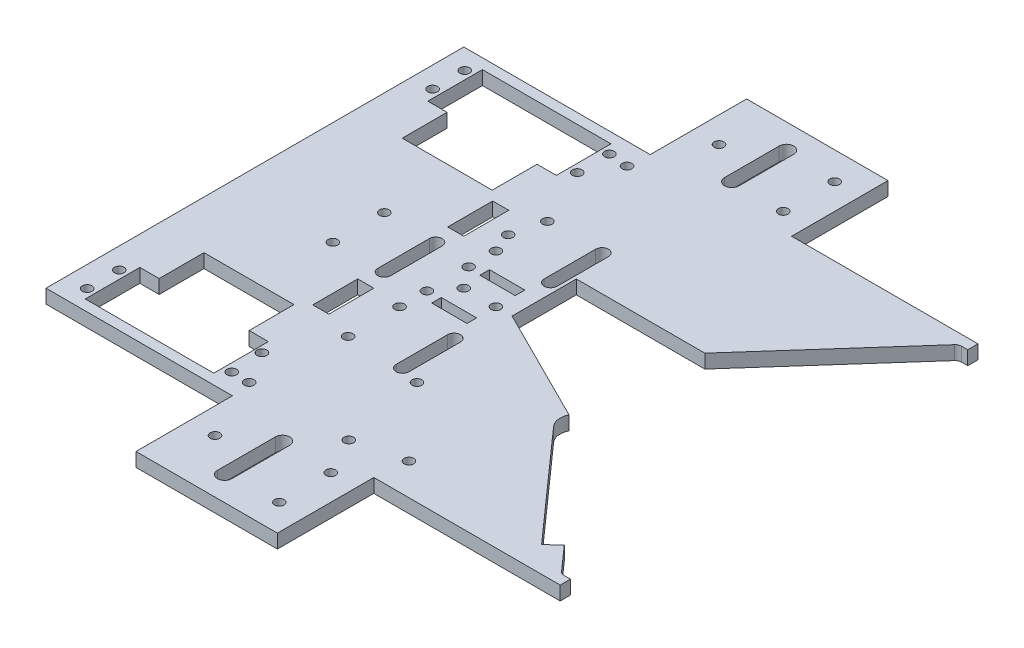
SolidWorks part; units mm, degrees
material "Acrylic (Medium-high impact)"
ref_plane "Front Plane" through (0, 0, 0) normal (0, 0, 1) x (1, 0, 0)
ref_plane "Top Plane" through (0, 0, 0) normal (0, 1, 0) x (1, 0, 0)
ref_plane "Right Plane" through (0, 0, 0) normal (1, 0, 0) x (0, 0, -1)
sketch "Sketch2" plane through (0, 0, 0) normal (0, 1, 0) x (1, 0, 0)
  line L2 (0, 0) -> (0, 65)
  line L3 (0, 65) -> (58, 65)
  line L4 (160, 0) -> (160, 65)
  line L8 (0, 0) -> (160, 0)
  line L9 (102, 65) -> (160, 65)
  line L11 (102, 65) -> (102, 95)
  line L12 (58, 65) -> (58, 95)
  line L13 (58, 95) -> (102, 95)
  dimension "D1" = 65
  dimension "D2" = 160
  dimension "D3" = 44
  dimension "D4" = 30
extrude "Boss-Extrude1" add sketch "Sketch2" along normal blind 4.3
mirror "Mirror1" about plane through (0, 4.3, 0) normal (0, 0, -1) of bodies 101
sketch "Sketch3" plane through (0, 4.3, 0) normal (0, 1, 0) x (1, 0, 0)
  line L0 (160, 61.8) -> (160, -61.8)
  line L1 (120.0126, 20) -> (157.1565, 61.8)
  line L3 (80.0126, 0) -> (80.0126, 20)
  line L4 (80.0126, 20) -> (120.0126, 20)
  line L12 (160, 65) -> (102, 65)
  line L13 (102, 65) -> (102, 95)
  line L15 (102, 95) -> (58, 95)
  line L16 (58, 65) -> (0, 65)
  line L17 (0, 65) -> (0, -65)
  line L18 (0, -65) -> (58, -65)
  line L20 (58, 95) -> (58, 65)
  line L22 (102, -65) -> (160, -65)
  line L23 (160, -65) -> (160, 65)
  line L36 (58, -65) -> (58, -95)
  line L38 (58, -95) -> (102, -95)
  line L39 (58, -95) -> (102, -95)
  line L40 (102, -95) -> (102, -65)
  line L42 (160, -61.8) -> (157.1556, -61.8)
  line L45 (160, 61.8) -> (157.1565, 61.8)
  line L48 (80.0126, 0) -> (120, -20)
  line L49 (120, -20) -> (157.1556, -61.8)
  line M24 (160, -65) -> (160, 65)
  dimension "D2" = 130
  dimension "D3" = 20
  dimension "D4" = 40
  dimension "D1" = 0
extrude "Cut-Extrude1" cut sketch "Sketch3" against normal blind 4.5 contours L48 L49 L1 L4 L3 M24 region at (132.7054, 4.3, -1.1594)
fillet "Fillet1" radius 2 2 edges at (157.1565, 2.15, -61.8) (157.1556, 2.15, 61.8)
ref_axis "Axis1" through (80, 4.3, 95) along (0, 0, -1)
sketch "Sketch4" plane through (0, 4.3, 0) normal (0, 1, 0) x (1, 0, 0)
  line L0 (80, -95) -> (80, 95)
  line L1 (102, -95) -> (58, -95) construction
  line L2 (102, 95) -> (58, 95) construction
ref_plane "Plane2" through (0, 4.3, 0) normal (0, 1, 0) x (1, 0, 0)
sketch "Sketch6" plane through (0, 4.3, 0) normal (0, 1, 0) x (1, 0, 0)
  line L3 (9, -61.8) -> (49, -61.8)
  line L6 (29, -45.8) -> (29, -44.8)
  line L7 (9, -44.8) -> (15, -44.8)
  line L11 (43, -44.8) -> (43, -30.8418)
  line L12 (15, -44.8) -> (15, -30.8418)
  line L13 (15, -30.8418) -> (43, -30.8418)
  line L15 (0, 0) -> (80.0126, 0)
  line L16 (80.0126, 0) -> (120, -20) construction
  line L18 (9, 44.8) -> (15, 44.8)
  line L20 (15, 30.8418) -> (43, 30.8418)
  line L21 (15, 44.8) -> (15, 30.8418)
  line L22 (43, 44.8) -> (43, 30.8418)
  line L25 (15, -45.8) -> (15, -30.8418) construction
  line L27 (9, 61.8) -> (49, 61.8)
  line L30 (4, -61.8) -> (3, -61.8)
  line L31 (0, -61.8) -> (160, -61.8) construction
  line L32 (3, -61.8) -> (4, -61.8)
  line L33 (3, -44.8) -> (3, -62.8) construction
  line L34 (3, -62.8) -> (55, -62.8) construction
  line L35 (55, -44.8) -> (55, -62.8) construction
  line L36 (4, -61.8) -> (54, -61.8) construction
  line L37 (0, 61.8) -> (160, 61.8) construction
  line L38 (54, 61.8) -> (55, 61.8)
  line L39 (54, 61.8) -> (55, 61.8)
  line L40 (43, 44.8) -> (49, 44.8)
  line L41 (4, -45.8) -> (4, -61.8) construction
  line L42 (4, -45.8) -> (54, -45.8) construction
  line L43 (43, -44.8) -> (49, -44.8)
  line L44 (3, -44.8) -> (55, -44.8) construction
  line L45 (29, -45.8) -> (29, -30.8418) construction
  line L46 (43, -45.8) -> (43, -30.8418) construction
  line L47 (54, -45.8) -> (54, -61.8) construction
  line L48 (9, -61.8) -> (49, -61.8)
  line L52 (9, 61.8) -> (9, 44.8)
  line L53 (55, 61.8) -> (54, 61.8)
  line L56 (49, 61.8) -> (49, 44.8)
  line L59 (3, -61.8) -> (4, -61.8)
  line L60 (9, -44.8) -> (9, -61.8)
  line L64 (49, -44.8) -> (49, -61.8)
  dimension "D4" = 1
  dimension "D5" = 14
  dimension "D6" = 14
extrude "Cut-Extrude2" cut sketch "Sketch6" against normal blind 10
sketch "Sketch8" plane through (0, 4.3, 0) normal (0, 1, 0) x (1, 0, 0)
  circle A0 centre (6.5, 58.8) radius 1.5
  circle A1 centre (6.5, 48.8) radius 1.5
  circle A2 centre (51.5, 48.8) radius 1.5
  circle A3 centre (51.5, 58.8) radius 1.5
  circle A4 centre (6.5, -48.7) radius 1.5
  circle A5 centre (6.5, -58.7) radius 1.5
  circle A6 centre (51.5, -58.7) radius 1.5
  circle A7 centre (51, -48.8) radius 1.5
  dimension "D7" = 3
extrude "Cut-Extrude3" cut sketch "Sketch8" against normal blind 10
sketch "Sketch9" plane through (0, 0, 0) normal (0, -1, 0) x (1, 0, 0)
  line L0 (75.75, 69.4) -> (75.75, 87.4)
  line L1 (75.75, -87.4) -> (75.75, -70.4)
  line L2 (80.25, -87.4) -> (80.25, -70.4)
  line L4 (80.25, 69.4) -> (80.25, 87.4)
  circle A0 centre (94, 70.4) radius 1.5
  circle A1 centre (66, 78.4) radius 1.5
  circle A2 centre (66, -78.4) radius 1.5
  circle A3 centre (94, -86.4) radius 1.5
  circle A4 centre (94, 86.4) radius 1.5
  circle A5 centre (94, -70.4) radius 1.5
  arc A6 (75.75, -87.4) -> (80.25, -87.4) centre (78, -87.4) ccw
  arc A7 (80.25, -70.4) -> (75.75, -70.4) centre (78, -70.4) ccw
  arc A10 (75.75, 69.4) -> (80.25, 69.4) centre (78, 69.4) ccw
  arc A12 (80.25, 87.4) -> (75.75, 87.4) centre (78, 87.4) ccw
  dimension "D1" = 3
extrude "Cut-Extrude4" cut sketch "Sketch9" against normal blind 10
sketch "Sketch7" plane through (0, 4.3, 0) normal (0, 1, 0) x (1, 0, 0)
  line L0 (0, 0) -> (80.0126, 0)
  line L1 (0, 65) -> (0, -65) construction
  line L2 (80.0126, 0) -> (80.0126, 20) construction
  line L3 (80, -95) -> (80, 95) construction
  line L4 (64, -9) -> (75, -9)
  line L5 (64, -6) -> (75, -6)
  line L6 (64, -9) -> (64, -6)
  line L7 (75, -9) -> (75, -6)
  line L8 (64, -7.5) -> (75, -7.5)
  line L9 (64, 7.5) -> (75, 7.5)
  line L10 (75, 9) -> (75, 6)
  line L11 (64, 9) -> (64, 6)
  line L12 (64, 6) -> (75, 6)
  line L13 (64, 9) -> (75, 9)
  circle A0 centre (60.0126, -6.5) radius 1.5
  circle A1 centre (60.0126, 6.5) radius 1.5
  dimension "D1" = 3
  dimension "D2" = 6.5
  dimension "D3" = 20
  dimension "D6" = 11
  dimension "D4" = 5
  dimension "D5" = 3
  dimension "D7" = 7.5
sketch "Sketch10" plane through (0, 4.3, 0) normal (0, 1, 0) x (1, 0, 0)
  line L0 (120, -20) -> (156.5589, -61.1287) construction
  line L1 (123.3218, -23.737) -> (149.8964, -53.6334)
  line L2 (116.263, -23.3218) -> (146.1593, -56.9552)
  line L3 (149.8964, -53.6334) -> (146.1593, -56.9552)
  line L4 (120, -20) -> (156.5589, -61.1287) construction
  line L5 (116.263, -23.3218) -> (152.8218, -64.4505) construction
  arc A0 (123.3218, -23.737) -> (116.263, -23.3218) centre (120, -20) ccw
  dimension "D1" = 5
  dimension "D2" = 45
extrude "Cut-Extrude5" cut sketch "Sketch10" against normal blind 10
sketch "Sketch11" plane through (0, 0, 0) normal (0, -1, 0) x (1, 0, 0)
  line L0 (0, 0) -> (80.0126, 0) construction
  line L1 (80, 95) -> (80, -95) construction
  line L2 (80.0126, 0) -> (0, 0)
  line L4 (75, 31.0313) -> (75, 15.0313)
  line L6 (79, 31.0313) -> (79, 15.0313)
  line L7 (79, -31.0313) -> (79, -15.0313)
  line L8 (75, -31.0313) -> (75, -15.0313)
  circle A0 centre (60, 31) radius 1.5
  circle A1 centre (60, 15) radius 1.5
  arc A2 (75, 31.0313) -> (79, 31.0313) centre (77, 31.0313) cw
  arc A3 (75, 15.0313) -> (79, 15.0313) centre (77, 15.0313) ccw
  arc A4 (75, -15.0313) -> (79, -15.0313) centre (77, -15.0313) cw
  arc A5 (75, -31.0313) -> (79, -31.0313) centre (77, -31.0313) ccw
  circle A6 centre (60, -15) radius 1.5
  circle A7 centre (60, -31) radius 1.5
  dimension "D1" = 3
  dimension "D2" = 16
  dimension "D3" = 15
  dimension "D4" = 20
  dimension "D5" = 15
  dimension "D6" = 4
extrude "Cut-Extrude6" cut sketch "Sketch11" against normal blind 10 contours L4 A3 L6 A2 | L8 A5 L7 A4 | A7 | A0 | A1 | A6 region at (77, 0, 23.0313) region at (77, 0, -23.0313) region at (60, 0, -31)
sketch "Sketch12" plane through (0, 0, 0) normal (0, -1, 0) x (-1, 0, 0)
  line L0 (0, 0) -> (-80.0126, 0) construction
  line L3 (-50.2627, -8) -> (-50.2627, 8)
  line L4 (-50.2627, 0) -> (-46.2627, 0)
  line L5 (-46.2627, -8) -> (-46.2627, 8)
  line L6 (0, 0) -> (-46.2627, 0)
  line L7 (0, 65) -> (0, -65) construction
  line L8 (-160, -61.8) -> (0, -61.8) construction
  line L9 (-80.0126, 0) -> (-50.2627, 0)
  line L10 (-80.0126, 0) -> (-115.5281, -17.7634) construction
  line L11 (-80.0126, 0) -> (-80.0126, 20) construction
  line L12 (-58, -65) -> (0, -65) construction
  line L13 (-58, 65) -> (0, 65) construction
  circle A0 centre (-32.2627, -8) radius 1.5
  circle A1 centre (-32.2627, 8) radius 1.5
  arc A2 (-46.2627, 8) -> (-50.2627, 8) centre (-48.2627, 8) ccw
  arc A3 (-50.2627, -8) -> (-46.2627, -8) centre (-48.2627, -8) ccw
  circle A5 centre (-32.2627, -8) radius 1.5 construction
  circle A6 centre (-32.2627, 8) radius 1.5 construction
  dimension "D1" = 3
  dimension "D8" = 8
  dimension "D9" = 8
  dimension "D2" = 8
  dimension "D3" = 14
  dimension "D4" = 4
  dimension "D5" = 61.8
  dimension "D6" = 65
  dimension "D7" = 65
extrude "Cut-Extrude7" cut sketch "Sketch12" against normal blind 10 contours A3 L5 L4 L3 | L4 L5 A2 L3 | A0 | A1 region at (48.2627, 0, 4.7958) region at (48.2627, 0, -4.7958) region at (32.2627, 0, 8) region at (32.2627, 0, -8)
extrude "Cut-Extrude8" cut sketch "Sketch7" against normal blind 9 contours A0 | L4 L7 L5 L6 | L12 L10 L13 L11 | A1
sketch "Sketch13" plane through (0, 4.3, 0) normal (0, 1, 0) x (1, 0, 0)
  line L0 (80.0126, 0) -> (59.0194, 0)
  line L1 (80, -95) -> (80, 95) construction
  circle A0 centre (65, 0) radius 1.5
  circle A1 centre (75, 0) radius 1.5
  dimension "D2" = 3
  dimension "D3" = 5
  dimension "D1" = 10
extrude "Cut-Extrude9" cut sketch "Sketch13" against normal blind 10 contours L0 A0 | L0 A0 | L0 A1 | L0 A1 region at (75, 4.3, 0.6366) region at (75, 4.3, -0.6366) region at (65, 4.3, 0.6366) region at (65, 4.3, -0.6366)
sketch "Sketch14" plane through (0, 4.3, 0) normal (0, 1, 0) x (1, 0, 0)
  circle A0 centre (57.5, 58.3) radius 1.5
  circle A2 centre (57.5, 21.3) radius 1.5
  circle A3 centre (83.1278, -32.706) radius 1.5
  circle A4 centre (103.0587, -55.1282) radius 1.5
  dimension "D1" = 3
  dimension "D2" = 3
extrude "Cut-Extrude10" cut sketch "Sketch14" against normal blind 10
sketch "Sketch15" plane through (0, 4.3, 0) normal (0, 1, 0) x (1, 0, 0)
  line L1 (46, 28) -> (51, 28)
  line L2 (46, 28) -> (46, 14)
  line L3 (46, 14) -> (51, 14)
  line L4 (51, 28) -> (51, 14)
  line L6 (0, 65) -> (0, -65) construction
  line L7 (80.0126, 0) -> (53.7017, 0)
  line L8 (46, -14) -> (51, -14)
  line L9 (51, -28) -> (51, -14)
  line L10 (46, -28) -> (51, -28)
  line L11 (46, -28) -> (46, -14)
  arc A0 (50.2627, 8) -> (46.2627, 8) centre (48.2627, 8) ccw construction
  arc A1 (46.2627, -8) -> (50.2627, -8) centre (48.2627, -8) ccw construction
  dimension "D1" = 46
  dimension "D2" = 5
  dimension "D3" = 14
  dimension "D4" = 14
  dimension "D5" = 14
  dimension "D6" = 6
  dimension "D7" = 6
extrude "Cut-Extrude11" cut sketch "Sketch15" against normal blind 10 contours L4 L1 L2 L3 | L11 L10 L9 L8 region at (48.5, 4.3, -21) region at (48.5, 4.3, 21)
sketch "Sketch16" plane through (0, 4.3, 0) normal (0, 1, 0) x (1, 0, 0)
  circle A0 centre (88, -58.8) radius 1.5
  circle A1 centre (57, -58.8) radius 1.5
  dimension "D1" = 3
extrude "Cut-Extrude12" cut sketch "Sketch16" against normal blind 10
ref_plane "Plane3" through (44.2426, 0, 0) normal (1, 0, 0) x (0, 0, -1)
sketch "Sketch17" plane through (44.2426, 0, 0) normal (1, 0, 0) x (0, 0, -1)
  line L4 (0, 0) -> (20, 0)
  line L5 (20, 0) -> (20, 4.3)
  line L6 (20, 4.3) -> (0, 4.3)
  line L7 (0, 4.3) -> (0, 0)
  line L8 (0, 0) -> (20, 0)
  line L9 (20, 0) -> (20, 4.3)
  line L10 (20, 4.3) -> (0, 4.3)
  line L11 (0, 4.3) -> (0, 0)
  circle A0 centre (-2.83, 16.28) radius 0.5
  point P6 (0, 2.15)
  dimension "D4" = 1
  dimension "D2" = 2.83
  dimension "D3" = 14.13
  dimension "D1" = 0
